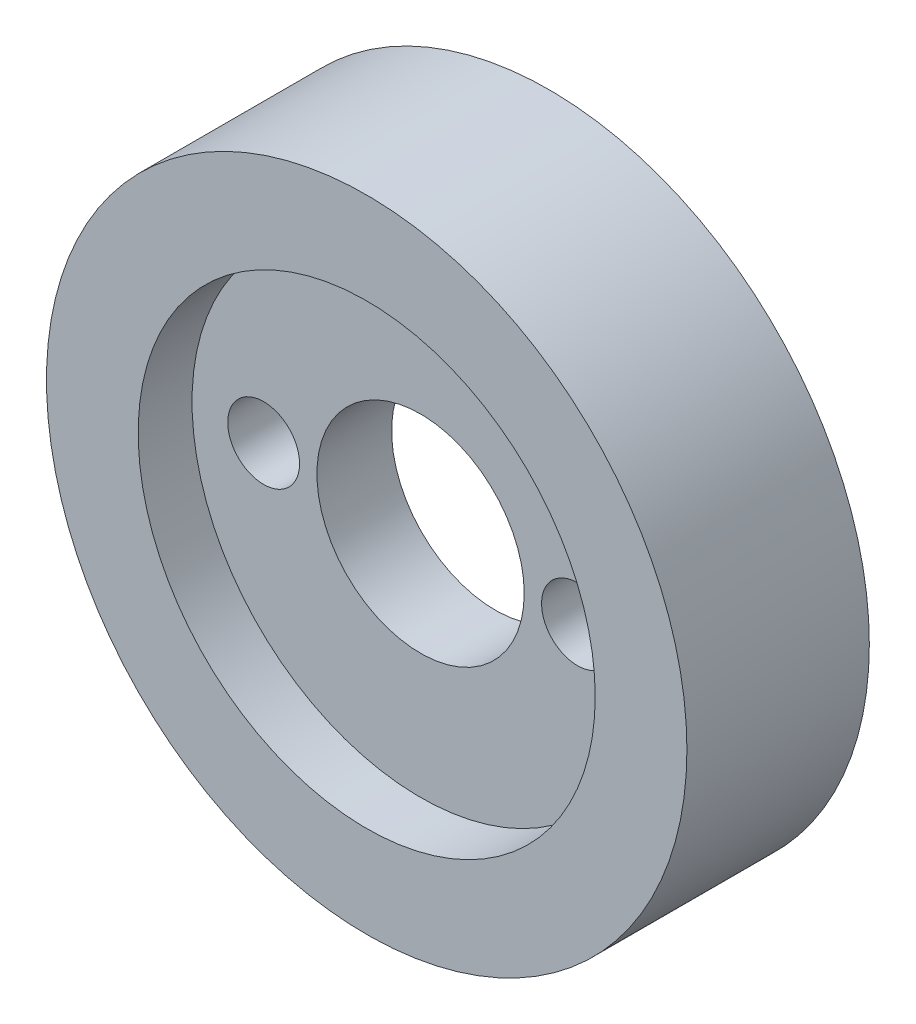
SolidWorks part; units mm, degrees
ref_plane "Front Plane" through (0, 0, 0) normal (0, 0, 1) x (1, 0, 0)
ref_plane "Top Plane" through (0, 0, 0) normal (0, 1, 0) x (1, 0, 0)
ref_plane "Right Plane" through (0, 0, 0) normal (1, 0, 0) x (0, 0, -1)
sketch "Sketch1" plane through (0, 0, 0) normal (0, 0, 1) x (1, 0, 0)
  circle A0 centre (0, 0) radius 9.8091
  circle A1 centre (0, 0) radius 3.175
  dimension "D1" = 19.6182
  dimension "D2" = 6.35
extrude "Boss-Extrude1" add sketch "Sketch1" along normal mid plane 5.588
sketch "Sketch2" plane through (0, 0, 2.794) normal (0, 0, 1) x (1, 0, 0)
  line L0 (0, 0) -> (0, 1.2313) construction
  line L1 (-7, 0) -> (-3.075, 0)
  circle A0 centre (0, 0) radius 7
  circle A1 centre (0, 0) radius 3.075
  circle A2 centre (-4.8069, 0) radius 1.1
  circle A3 centre (4.8069, 0) radius 1.1
  circle M2 centre (0, 0) radius 3.175
  dimension "D1" = 14
  dimension "D2" = 6.15
  dimension "D3" = 2.2
  dimension "D4" = 9.6139
extrude "Cut-Extrude1" cut sketch "Sketch2" against normal blind 1.65 contours A2 A0 A3 M2 region at (0, 6.802, 2.794)
mirror "Mirror1" about plane through (0, 0, 0) normal (0, 0, 1) of "Cut-Extrude1"
extrude "Cut-Extrude2" cut sketch "Sketch2<3>" against normal through all contours L1 A2 | L1 A2 | A3 region at (-4.8069, -0.4669, 2.794) region at (-4.8069, 0.4669, 2.794) region at (4.8069, 0, 2.794)
sketch "Sketch2<3>" plane through (0, 0, 2.794) normal (0, 0, 1) x (1, 0, 0) same geometry as "Sketch2"
